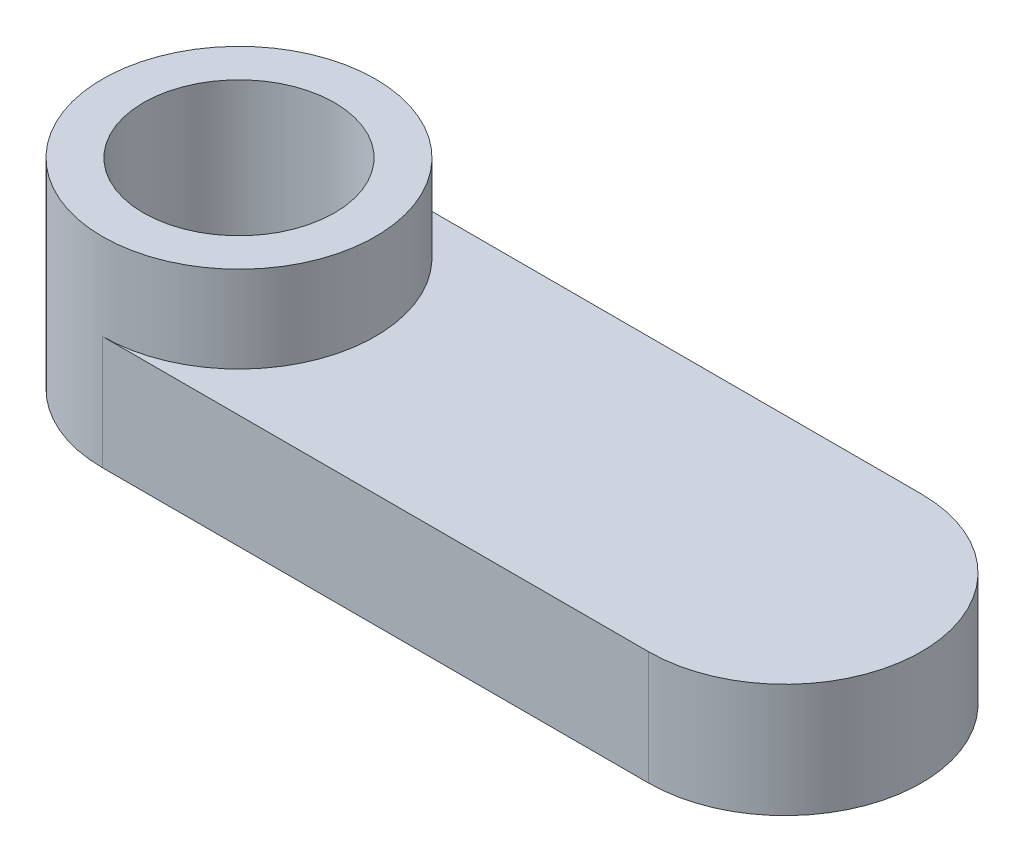
SolidWorks part; units mm, degrees
ref_plane "前视基准面" through (0, 0, 0) normal (0, 0, 1) x (1, 0, 0)
ref_plane "上视基准面" through (0, 0, 0) normal (0, 1, 0) x (1, 0, 0)
ref_plane "右视基准面" through (0, 0, 0) normal (1, 0, 0) x (0, 0, -1)
other "Configuration Table"
sketch "草图1" plane through (0, 0, 0) normal (0, 1, 0) x (1, 0, 0)
  line L0 (0, 0) -> (12, 0) construction
  line L1 (0, 3) -> (12, 3)
  line L2 (0, -3) -> (12, -3)
  arc A0 (0, 3) -> (0, -3) centre (0, 0) ccw
  arc A1 (12, -3) -> (12, 3) centre (12, 0) ccw
  circle A2 centre (0, 0) radius 2.1
  circle A4 centre (0, 0) radius 3
  point P3 (6, 0)
  dimension "D1" = 4.2
  dimension "D2" = 3
  dimension "D3" = 12
extrude "凸台-拉伸2" add sketch "草图1" along normal blind 2.5 contours A4 L2 A1 L1 region at (8.3562, 0, 0)
extrude "凸台-拉伸3" add sketch "草图1<4>" along normal blind 4.4 contours A2 A4 A0 region at (2.0613, 0, -2.0613)
sketch "草图1<4>" plane through (0, 0, 0) normal (0, 1, 0) x (1, 0, 0) same geometry as "草图1"
